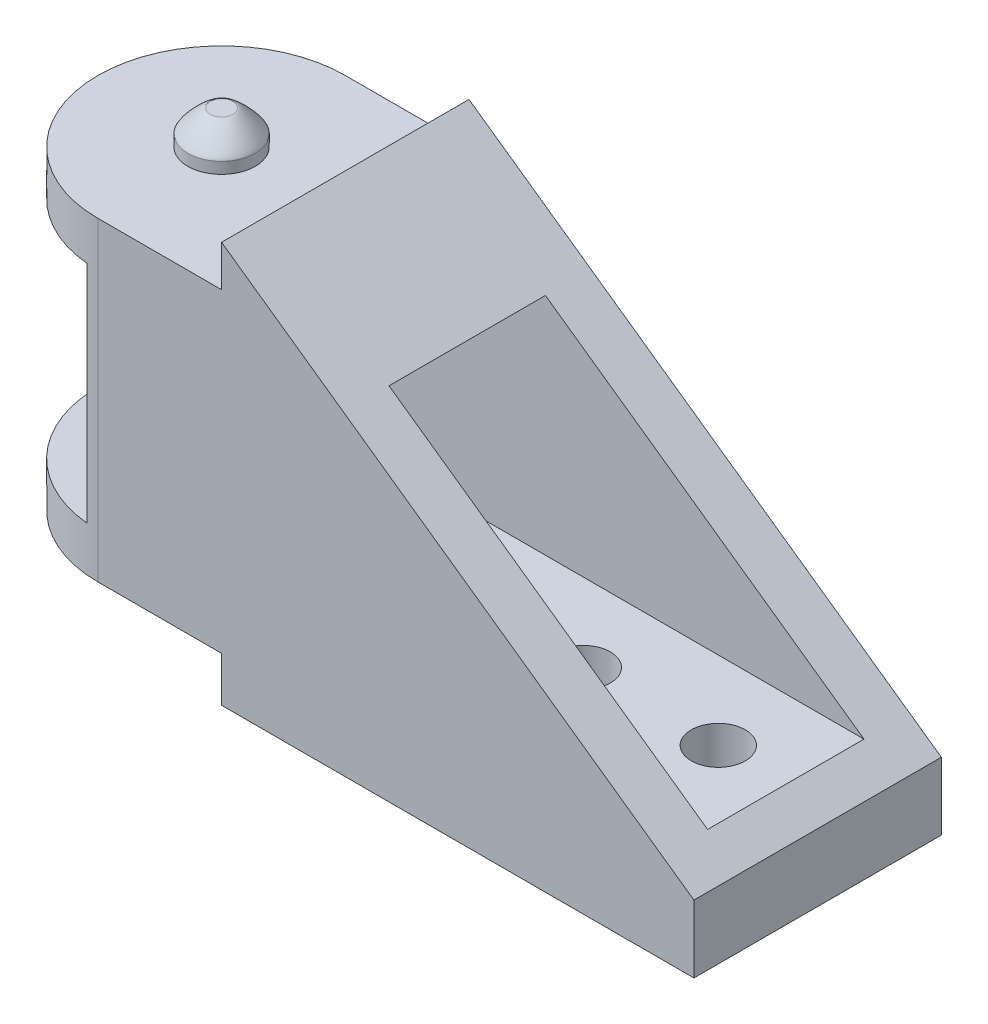
SolidWorks part; units mm, degrees
ref_plane "Front Plane" through (0, 0, 0) normal (0, 0, 1) x (1, 0, 0)
ref_plane "Top Plane" through (0, 0, 0) normal (0, 1, 0) x (1, 0, 0)
ref_plane "Right Plane" through (0, 0, 0) normal (1, 0, 0) x (0, 0, -1)
sketch "Croquis1" plane through (0, 0, 0) normal (0, 0, 1) x (1, 0, 0)
  line L0 (-5, 7) -> (5, 7)
  line L1 (5, 7) -> (5, 9)
  line L2 (5, 9) -> (5.7552, 9)
  line L3 (5.7552, 9) -> (27, -6)
  line L4 (27, -6) -> (27, -9)
  line L5 (27, -9) -> (5, -9)
  line L6 (5, -9) -> (5, -7)
  line L7 (5, -7) -> (-5, -7)
  line L9 (-5, -5) -> (0, -5)
  line L10 (0, -5) -> (0, 5)
  line L11 (0, 5) -> (-5, 5)
  line L12 (-5, 5) -> (-5, 7)
  line L13 (-5, -5) -> (-5, -7)
  point P11 (0, 0)
  dimension "D1" = 18
  dimension "D2" = 32
  dimension "D3" = 10
  dimension "D4" = 10
  dimension "D5" = 5
  dimension "D6" = 5
  dimension "D7" = 2
  dimension "D8" = 2
  dimension "D9" = 3
  dimension "D10" = 2
  dimension "D11" = 2
  dimension "D12" = 26.0065
extrude "Saliente-Extruir1" add sketch "Croquis1" along normal blind 11
sketch "Croquis2" plane through (0, -7, 0) normal (0, -1, 0) x (1, 0, 0)
  line L0 (0.5, 11) -> (-5, 11)
  line L1 (-5, 11) -> (-5, 0)
  line L2 (-5, 0) -> (0.5, 0)
  circle A1 centre (0.5, 5.5) radius 5.5
  line M1 (-5, 0) -> (5, 0)
  line M3 (5, 11) -> (-5, 11)
  line M4 (-5, 11) -> (-5, 0)
extrude "Cortar-Extruir1" cut sketch "Croquis2" against normal blind 61 contours A1 M3 M4 | A1 L1 M1 region at (-3.7715, -7, 9.7715) region at (-3.7715, -7, 1.2285)
sketch "Croquis3" plane through (0, 0, 0) normal (-1, 0, 0) x (0, 0, 1)
  line L0 (2.0228, 5) -> (8.9772, 5)
  line L1 (2.0228, 5) -> (2.0228, -5)
  line L2 (8.9772, 5) -> (8.9772, -5)
  line L3 (2.0228, -5) -> (8.9772, -5)
  line L4 (2.0228, 5) -> (8.9772, -5) construction
  line L5 (8.9772, 5) -> (2.0228, -5) construction
  line L6 (0.0228, -5) -> (0.0228, 5) construction
  line L7 (10.9772, 5) -> (10.9772, -5) construction
  line L8 (10.9772, -5) -> (0.0228, -5) construction
  point P1 (5.5, 0)
  dimension "D1" = 2
  dimension "D2" = 2
extrude "Cortar-Extruir2" cut sketch "Croquis3" against normal blind 61
sketch "Croquis4" plane through (0, -5, 0) normal (0, 1, 0) x (1, 0, 0)
  line L0 (25.5837, -2.0228) -> (25.5837, -8.9772) construction
  circle A0 centre (22.5837, -5.5) radius 1.2
  circle A1 centre (16.5837, -5.5) radius 1.2
  point P14 (25.5837, -5.5)
  dimension "D3" = 2.4
  dimension "D4" = 2.4
  dimension "D1" = 6
  dimension "D2" = 3
extrude "Cortar-Extruir3" cut sketch "Croquis4" against normal blind 61
sketch "Croquis5" plane through (0, 7, 0) normal (0, 1, 0) x (1, 0, 0)
  circle A0 centre (0.5, -5.5) radius 1.5
  dimension "D1" = 3
extrude "Saliente-Extruir2" add sketch "Croquis5" along normal blind 1.5
mirror "Simetría4" about plane through (0, 0, 0) normal (0, 1, 0) of "Saliente-Extruir2"
fillet "Redondeo2" radius 1 1 edges at (-1, 8.5, 5.5) conic radius 5
fillet "Redondeo6" radius 1 1 edges at (-1, -8.5, 5.5) conic radius 5
sketch "Croquis6" plane through (0, 9, 0) normal (0, 1, 0) x (1, 0, 0)
  line L3 (5, -11) -> (5, 0)
  line L4 (5, 0) -> (6, 0)
  line L5 (6, 0) -> (6, -11)
  line L6 (6, -11) -> (5, -11)
  dimension "D1" = 1
extrude "Cortar-Extruir4" cut sketch "Croquis6" against normal blind 2
sketch "Croquis7" plane through (0, -9, 0) normal (0, -1, 0) x (1, 0, 0)
  line L0 (5, 0) -> (6, 0)
  line L1 (5, 0) -> (27, 0) construction
  line L2 (6, 0) -> (6, 11)
  line L3 (5, 11) -> (27, 11) construction
  line L4 (6, 11) -> (5, 11)
  line L5 (5, 11) -> (5, 0)
  dimension "D1" = 1
extrude "Cortar-Extruir5" cut sketch "Croquis7" against normal blind 2
